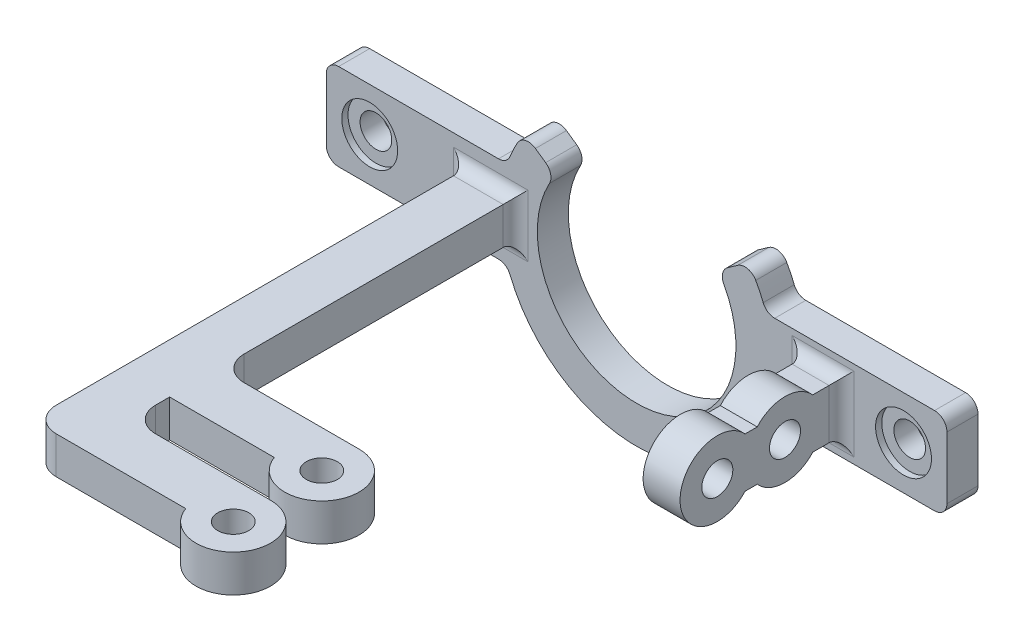
SolidWorks part; units mm, degrees
note: '?' marks a value the reader was unsure of.
ref_plane "Front Plane" through (0, 0, 0) normal (0, 0, 1) x (1, 0, 0)
ref_plane "Top Plane" through (0, 0, 0) normal (0, 1, 0) x (1, 0, 0)
ref_plane "Right Plane" through (0, 0, 0) normal (1, 0, 0) x (0, 0, -1)
sketch "Sketch1" plane through (0, 0, 0) normal (0, 0, 1) x (1, 0, 0)
  line L0 (100, 25) -> (100, 20)
  line L1 (100, 5) -> (100, 45) construction
  line L3 (98, 18) -> (72.2486, 18)
  line L4 (100, 25) -> (100, 30)
  line L5 (78.9438, 32) -> (98, 32)
  line L7 (78.9438, 32) -> (72.2486, 32)
  line L8 (54, 25) -> (106.793, 25) construction
  line L9 (50, 29) -> (50, 55.0668) construction
  line L16 (50, 25) -> (93.1322, 55.2015) construction
  line L17 (64.6534, 35.2604) -> (66.3009, 36.414)
  line L18 (50, 25) -> (6.8678, 55.2015) construction
  line L19 (46, 25) -> (-6.793, 25) construction
  line L20 (35.3466, 35.2604) -> (33.6991, 36.414)
  line L21 (21.0562, 32) -> (27.7514, 32)
  line L22 (2, 18) -> (27.7514, 18)
  line L23 (21.0562, 32) -> (2, 32)
  line L24 (0, 25) -> (0, 30)
  line L25 (0, 25) -> (0, 20)
  arc A0 (70.3945, 33.25) -> (69.1929, 35.7533) centre (50, 25) ccw
  arc A1 (35.955, 32.6641) -> (64.045, 32.6641) centre (50, 25) ccw
  arc A2 (29.6055, 16.75) -> (70.3945, 16.75) centre (50, 25) ccw
  circle A3 centre (93, 25) radius 2.55
  arc A14 (98, 32) -> (100, 30) centre (98, 30) cw
  arc A15 (98, 18) -> (100, 20) centre (98, 20) ccw
  arc A16 (72.2486, 18) -> (70.3945, 16.75) centre (72.2486, 16) ccw
  arc A17 (70.3945, 33.25) -> (72.2486, 32) centre (72.2486, 34) ccw
  arc A18 (64.6534, 35.2604) -> (64.045, 32.6641) centre (65.8006, 33.6221) ccw
  arc A19 (66.3009, 36.414) -> (69.1929, 35.7533) centre (67.4481, 34.7757) cw
  arc A21 (33.6991, 36.414) -> (30.8071, 35.7533) centre (32.5519, 34.7757) ccw
  arc A22 (35.3466, 35.2604) -> (35.955, 32.6641) centre (34.1994, 33.6221) cw
  arc A23 (29.6055, 33.25) -> (27.7514, 32) centre (27.7514, 34) cw
  arc A24 (27.7514, 18) -> (29.6055, 16.75) centre (27.7514, 16) cw
  arc A25 (2, 18) -> (0, 20) centre (2, 20) cw
  arc A26 (2, 32) -> (0, 30) centre (2, 30) ccw
  circle A27 centre (7, 25) radius 2.55
  arc A29 (29.6055, 33.25) -> (30.8071, 35.7533) centre (50, 25) cw
  point P30 (50, 3)
  point P31 (63.1064, 34.1772)
  point P35 (68.0213, 37.6187)
  point P39 (100, 32)
  point P73 (0, 32)
  point P74 (31.9787, 37.6187)
  point P75 (36.8936, 34.1772)
  dimension "D2" = 22
  dimension "D4" = 16
  dimension "D9" = 2
  dimension "D8" = 2
  dimension "D11" = 5.1
  dimension "D1" = 14
  dimension "D3" = 7
  dimension "D10" = 35
extrude "Boss-Extrude1" add sketch "Sketch1" along normal blind 5
fillet "Fillet2" [suppressed] radius 1
sketch "Sketch4" plane through (0, 0, 5) normal (0, 0, 1) x (1, 0, 0)
  circle A0 centre (93, 25) radius 4.5
  circle A1 centre (7, 25) radius 4.5
  dimension "D1" = 9
  dimension "D2" = 9
extrude "Cut-Extrude2" cut sketch "Sketch4" against normal blind 1
ref_axis "Axis1" through (93, 25, 4) along (0, 0, -1)?
ref_axis "Axis2" through (50, 25, 5) along (0, 0, -1)?
ref_plane "Plane1" through (0, 25, 0) normal (0, -1, 0) x (-1, 0, 0)
sketch "Sketch6" plane through (0, 25, 0) normal (0, -1, 0) x (-1, 0, 0)
  line L0 (-72.2486, -5) -> (-98, -5) construction
  line L1 (-77.0523, -5) -> (-83, -5)
  line L4 (-83, -5) -> (-83, -25)
  line L5 (-77.0523, -5) -> (-77.0523, -25)
  line L6 (-83, -25) -> (-77.0523, -25)
  line L7 (-93, -4) -> (-93, 0) construction
  dimension "D1" = 10
  dimension "D2" = 0
extrude "Boss-Extrude2" add sketch "Sketch6" along normal blind 4 and the other way blind 4
ref_plane "Plane2" through (77.0523, 21, 5) normal (1, 0, 0) x (0, 0, -1)
sketch "Sketch11" plane through (0, 0, 0) normal (0, 0, -1) x (-1, 0, 0)
  circle A0 centre (-93, 25) radius 4.5
  circle A1 centre (-7, 25) radius 4.5
  dimension "D1" = 9
  dimension "D2" = 9
extrude "Cut-Extrude3" cut sketch "Sketch11" against normal blind 0.5
thread "Thread1" [suppressed] pitch 0.8 start angle 0, offset 0, length 0, pitch 0.8, diameter 5.1
ref_plane "Plane3" through (90.45, 25, 4) normal (0, -1, 0) x (-1, 0, 0)
sketch "Thread Profile1" plane through (90.45, 25, 4) normal (0, -1, 0) x (-1, 0, 0)
  line L0 (0, 0) -> (0, 0.8) construction
  line L11 (0, 0) -> (0, 0.7)
  line L12 (0, 0.7) -> (-0.433, 0.45)
  line L13 (-0.433, 0.45) -> (-0.433, 0.25)
  line L15 (-0.433, 0.25) -> (0, 0)
  line L17 (-0.433, 0.35) -> (0, 0.35) construction
  point P2 (0, 0)
  dimension "Pitch" = 0.8
  dimension "Profile_Angle" = 60
  dimension "Profile_Land" = 0.2
  dimension "Profile_Height" = 0.433
sketch "Sketch16" plane through (0, 25, 0) normal (0, -1, 0) x (-1, 0, 0)
  line L0 (-27.7514, -5) -> (-2, -5) construction
  line L1 (-30.4943, -5) -> (-22.4943, -5)
  line L2 (-30.4943, -5) -> (-30.4943, -48.7321)
  line L3 (-30.4943, -75) -> (-26.4943, -75)
  line L4 (-22.4943, -5) -> (-22.4943, -71)
  line L5 (-30.4943, -60.7321) -> (-47.3614, -60.7321)
  line L6 (-30.4943, -75) -> (-47.3614, -75)
  line L8 (-34.4943, -67) -> (-53.0183, -67)
  line L10 (-53.0183, -52.7321) -> (-34.4943, -52.7321)
  line L11 (-30.4943, -60.7321) -> (-30.4943, -63)
  arc A0 (-53.0183, -67) -> (-47.3614, -75) centre (-53.0183, -73) ccw
  circle A1 centre (-53.0183, -73) radius 2.5
  arc A2 (-30.4943, -63) -> (-34.4943, -67) centre (-34.4943, -63) cw
  arc A3 (-26.4943, -75) -> (-22.4943, -71) centre (-26.4943, -71) ccw
  arc A4 (-53.0183, -52.7321) -> (-47.3614, -60.7321) centre (-53.0183, -58.7321) ccw
  circle A5 centre (-53.0183, -58.7321) radius 2.5
  arc A6 (-34.4943, -52.7321) -> (-30.4943, -48.7321) centre (-34.4943, -48.7321) ccw
  dimension "D5" = 5
  dimension "D6" = 4
  dimension "D7" = 4
  dimension "D8" = 12
  dimension "D10" = 5
  dimension "D11" = 4
  dimension "D1" = 0
  dimension "D2" = 70
  dimension "D3" = 8
  dimension "D4" = 6
  dimension "D9" = 8
extrude "Boss-Extrude3" add sketch "Sketch16" along normal blind 3 and the other way blind 3
fillet "Fillet3" radius 2 8 edges at (83, 25, 5) (80.0262, 29, 5) (77.0523, 25, 5) (80.0262, 21, 5) (26.4943, 22, 5) (30.4943, 25, 5) (22.4943, 25, 5) (26.4943, 28, 5)
sketch "Sketch17" plane through (83, 0, 0) normal (1, 0, 0) x (0, 0, -1)
  line L0 (-25, 29) -> (-25, 21) construction
  arc A0 (-19.5472, 27.5034) -> (-19.5472, 22.4966) centre (-25, 25) ccw
  arc A2 (-19.5472, 22.4966) -> (-19.5472, 27.5034) centre (-14.0944, 25) ccw
  dimension "D1" = 12
  dimension "D2" = 12
extrude "Boss-Extrude4" add sketch "Sketch17" against normal up to surface (5.9477 mm away) up to face at (77.0523, 25, 16)
sketch "Sketch18" plane through (83, 0, 0) normal (1, 0, 0) x (0, 0, -1)
  circle A0 centre (-25, 25) radius 2.5
  circle A1 centre (-14.0944, 25) radius 2.5
  dimension "D1" = 5
  dimension "D2" = 5
extrude "Cut-Extrude5" cut sketch "Sketch18" against normal up to next
thread "Thread2" [suppressed] pitch 0.8 start angle 0, offset 0, length 0, pitch 0.8, diameter 5.1
ref_plane "Plane4" through (4.45, 25, 4) normal (0, -1, 0) x (-1, 0, 0)
sketch "Thread Profile2" plane through (4.45, 25, 4) normal (0, -1, 0) x (-1, 0, 0)
  line L0 (0, 0) -> (0, 0.8) construction
  line L11 (0, 0) -> (0, 0.7)
  line L12 (0, 0.7) -> (-0.433, 0.45)
  line L13 (-0.433, 0.45) -> (-0.433, 0.25)
  line L15 (-0.433, 0.25) -> (0, 0)
  line L17 (-0.433, 0.35) -> (0, 0.35) construction
  point P2 (0, 0)
  dimension "Pitch" = 0.8
  dimension "Profile_Angle" = 60
  dimension "Profile_Land" = 0.2
  dimension "Profile_Height" = 0.433
equation "\"D3@Sketch1\"=\"D1@Sketch1\"/2"
